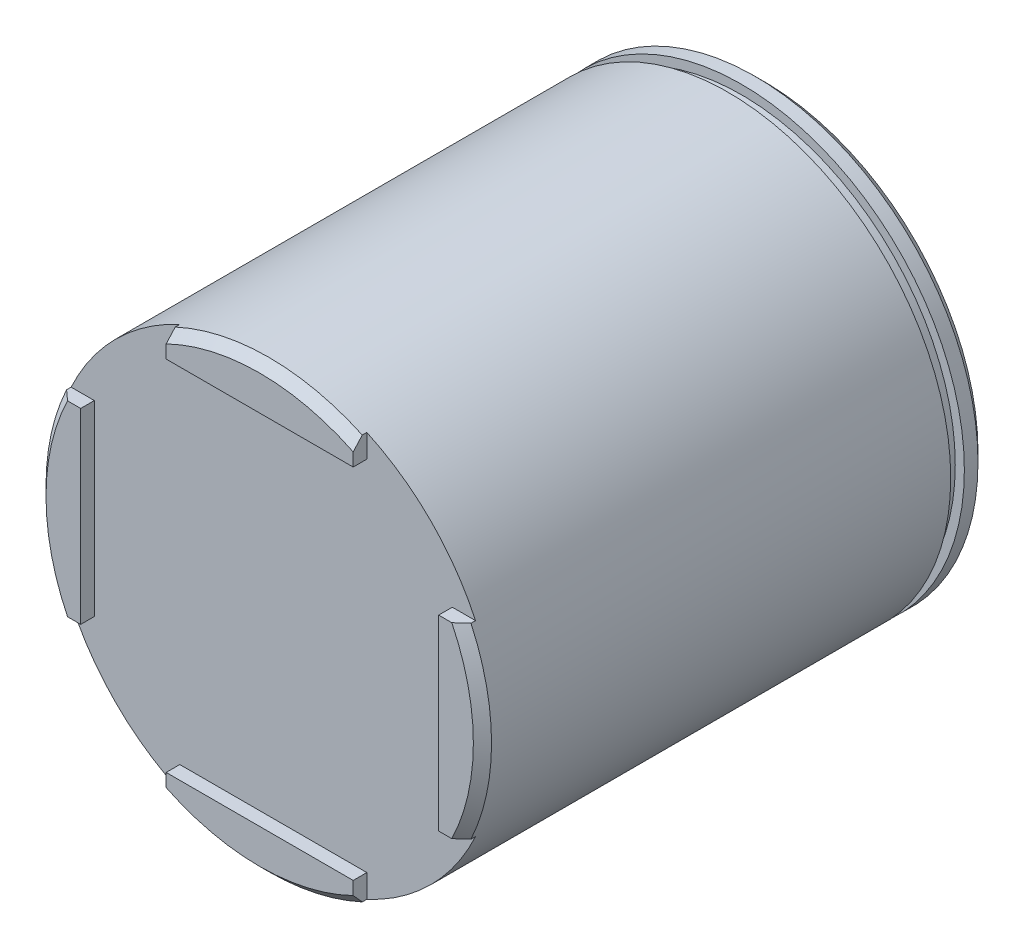
SolidWorks part; units mm, degrees
material "Copper"
ref_plane "Front Plane" through (0, 0, 0) normal (0, 0, 1) x (1, 0, 0)
ref_plane "Top Plane" through (0, 0, 0) normal (0, 1, 0) x (1, 0, 0)
ref_plane "Right Plane" through (0, 0, 0) normal (1, 0, 0) x (0, 0, -1)
sketch "Sketch1" plane through (0, 0, 0) normal (0, 0, 1) x (1, 0, 0)
  circle A0 centre (0, 8.255) radius 3
  circle A1 centre (7.149, 4.1275) radius 3
  circle A2 centre (7.149, -4.1275) radius 3
  circle A3 centre (0, -8.255) radius 3
  circle A4 centre (-7.149, -4.1275) radius 3
  circle A5 centre (-7.149, 4.1275) radius 3
  circle A6 centre (0, 0) radius 12.446
  point P15 (0, 0)
  dimension "D1" = 8.255
  dimension "D2" = 6
sketch "Sketch2" plane through (0, 0, 0) normal (0, 0, 1) x (1, 0, 0)
  circle A0 centre (0, 0) radius 12.446
extrude "Boss-Extrude1" add sketch "Sketch2" along normal blind 28.194
sketch "Sketch3" plane through (0, 0, 0) normal (0, 0, -1) x (-1, 0, 0)
  circle A0 centre (0, 8.255) radius 1.5875
  circle A1 centre (-7.149, 4.1275) radius 1.5875
  circle A2 centre (-7.149, -4.1275) radius 1.5875
  circle A3 centre (0, -8.255) radius 1.5875
  circle A4 centre (7.149, -4.1275) radius 1.5875
  circle A5 centre (7.149, 4.1275) radius 1.5875
  dimension "D1" = 3.175
chamfer "Chamfer1" distance 0.508 angle 45 2 edges at (12.446, 0, 28.194) (12.446, 0, 0)
hole_wizard "#45 (0.082) Diameter Hole1" positions "Sketch5" profile "Sketch4" hole size "#45" standard "ANSI Inch"
sketch "Sketch5" plane through (0, 0, 0) normal (0, 0, -1) x (-1, 0, 0)
  point P0 (0, 8.255)
  point P3 (-7.149, 4.1275)
  point P6 (-7.149, -4.1275)
  point P9 (0, -8.255)
  point P12 (7.149, -4.1275)
  point P15 (7.149, 4.1275)
sketch "Sketch4" plane through (0, 8.255, 0) normal (1, 0, 0) x (0, 1, 0)
  line L0 (0, 0) -> (0, 22.0214)
  line L1 (0, 22.0214) -> (1.0414, 21.59)
  line L2 (1.0414, 21.59) -> (1.0414, 0)
  line L5 (1.0414, 0) -> (0, 0)
  line L10 (0, 22.0214) -> (-1.0414, 21.59) construction
  line L11 (0, -6.35) -> (0, 107.95) construction
  dimension "Hole Dia." = 2.0828
  dimension "Hole Depth" = 21.59
  dimension "Drill Angle" = 135
sketch "Sketch8" plane through (0, 0, 0) normal (0, 0, 1) x (1, 0, 0)
  line L0 (0, 12.446) -> (0, 0)
  circle A0 centre (0, 0) radius 12.446 construction
ref_axis "Axis3" through (0, 8.255, 21.59) along (0, 0, -1)
ref_plane "Plane1" through (0, 0, 0) normal (1, 0, 0) x (0, 0, -1)
ref_axis "Axis2" through (0, 0, 27.686) along (0, 0, -1)
sketch "Sketch11" plane through (0, 0, 28.194) normal (0, 0, 1) x (1, 0, 0)
  line L1 (-10, 10) -> (10, 10)
  line L2 (-10, 10) -> (-10, -10)
  line L3 (-10, -10) -> (10, -10)
  line L4 (10, 10) -> (10, -10)
  line L5 (-10, 10) -> (10, -10) construction
  line L6 (-10, -10) -> (10, 10) construction
  point P0 (0, 0)
  dimension "D1" = 20
extrude "Cut-Extrude1" cut sketch "Sketch11" against normal blind 0.762
sketch "Sketch13" plane through (0, 0, 28.194) normal (0, 0, 1) x (1, 0, 0)
  line L0 (-11.2962, 5.2248) -> (11.2962, 5.2248)
  line L1 (7.4097, 10) -> (-7.4097, 10) construction
  line L2 (-11.2962, 5.2248) -> (-11.2962, 10)
  line L3 (-11.2962, 10) -> (11.2962, 10)
  line L4 (11.2962, 10) -> (11.2962, 5.2248)
  line L5 (0, 0) -> (-20.1602, 0) construction
  line L6 (11.2962, -10) -> (11.2962, -5.2248)
  line L7 (-11.2962, -10) -> (11.2962, -10)
  line L8 (-11.2962, -5.2248) -> (-11.2962, -10)
  line L9 (-11.2962, -5.2248) -> (11.2962, -5.2248)
  line L10 (6.5204, 10) -> (-6.5204, 10) construction
  arc A0 (-10, 7.4097) -> (-10, -7.4097) centre (0, 0) ccw construction
  arc A1 (10, 7.4097) -> (10, -7.4097) centre (0, 0) ccw construction
  dimension "D1" = 4.7752
extrude "Cut-Extrude2" cut sketch "Sketch13" against normal up to surface (0.762 mm away) up to face at (0, 0, 27.432)
sketch "Sketch14" plane through (0, 0, 28.194) normal (0, 0, 1) x (1, 0, 0)
  line L0 (-5.2248, 11.2962) -> (-5.2248, -11.2962)
  line L1 (-10, 5.2248) -> (-10, -5.2248) construction
  line L2 (-5.2248, -11.2962) -> (-10, -11.2962)
  line L3 (-10, -11.2962) -> (-10, 11.2962)
  line L4 (-10, 11.2962) -> (-5.2248, 11.2962)
  line L5 (0, 0) -> (0, -21.9627) construction
  line L6 (10, 11.2962) -> (5.2248, 11.2962)
  line L7 (10, -11.2962) -> (10, 11.2962)
  line L8 (5.2248, -11.2962) -> (10, -11.2962)
  line L9 (5.2248, 11.2962) -> (5.2248, -11.2962)
  arc A0 (7.4097, 10) -> (-7.4097, 10) centre (0, 0) ccw construction
  arc A1 (-7.4097, -10) -> (7.4097, -10) centre (0, 0) ccw construction
  dimension "D1" = 4.7752
extrude "Cut-Extrude3" cut sketch "Sketch14" against normal up to surface (0.762 mm away) up to face at (0, 0, 27.432)
sketch "Sketch16" plane through (0, 0, 0) normal (0, 0, -1) x (-1, 0, 0)
  line L0 (0, 0) -> (0, 11.938)
  line L1 (0, 0) -> (10.3386, 5.969)
  line L2 (0, 0) -> (10.3386, -5.969)
  line L3 (0, 0) -> (0, -11.938)
  line L4 (0, 0) -> (-10.3386, -5.969)
  line L5 (0, 0) -> (-10.3386, 5.969)
  circle A0 centre (0, 0) radius 11.938 construction
  point P13 (0, 0)
  dimension "D1" = 6
sketch "Sketch17" plane through (0, 0, 0) normal (1, 0, 0) x (0, 0, -1)
  line L0 (-20.5103, 8.255) -> (-20.5103, 9.271)
  line L1 (-21.59, 8.255) -> (0, 8.255) construction
  line L2 (-20.5103, 9.271) -> (-7.62, 11.255)
  line L4 (-7.62, 11.255) -> (-7.62, 8.255) construction
  line L5 (-7.62, 11.255) -> (0, 11.255)
  line L6 (0, 11.255) -> (0, 8.255)
  line L7 (0, 8.255) -> (-7.62, 8.255)
  line L8 (-20.5103, 8.255) -> (-7.62, 8.255)
  line L9 (0, -11.938) -> (0, 11.938) construction
  line L10 (0, 7.2136) -> (0, 9.2964) construction
  point P12 (0, 7.2136)
  point P13 (0, 9.2964)
  dimension "D1" = 8.75
  dimension "D2" = 1.016
  dimension "D3" = 7.62
  dimension "D4" = 3
revolve "Cut-Revolve2" cut sketch "Sketch17" angle 360 about L8
pattern_circular "CirPattern2" count 6 over 360 about axis through (0, 0, 27.686) along (0, 0, -1) of "Cut-Revolve2"
ref_plane "Plane2" through (0, 0, 0) normal (1, 0, 0) x (0, 0, -1)
sketch "Sketch18" plane through (0, 0, 0) normal (1, 0, 0) x (0, 0, -1)
  line L0 (-0.508, 12.446) -> (-27.686, 12.446) construction
  line L1 (-1.27, 12.446) -> (-2.032, 12.446)
  line L2 (-1.27, 12.446) -> (-1.27, 11.938)
  line L3 (-1.27, 11.938) -> (-2.032, 11.938)
  line L4 (-2.032, 12.446) -> (-2.032, 11.938)
  line L5 (0, 0) -> (0, 11.938) construction
  dimension "D1" = 0.762
  dimension "D2" = 1.27
  dimension "D3" = 0.508
revolve "Cut-Revolve3" cut sketch "Sketch18" angle 360 about axis through (0, 0, 27.686) along (0, 0, -1)
